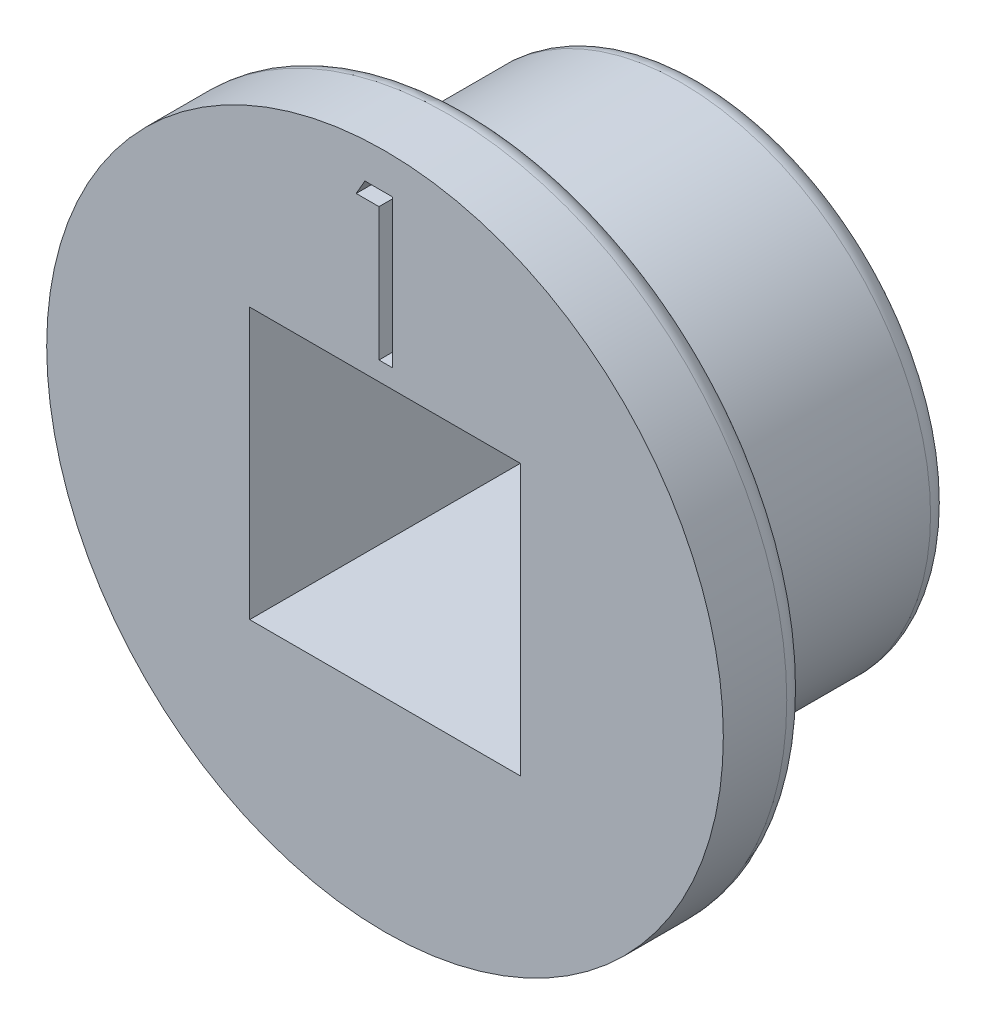
SolidWorks part; units mm, degrees
material "ABS"
ref_plane "Front Plane" through (0, 0, 0) normal (0, 0, 1) x (1, 0, 0)
ref_plane "Top Plane" through (0, 0, 0) normal (0, 1, 0) x (1, 0, 0)
ref_plane "Right Plane" through (0, 0, 0) normal (1, 0, 0) x (0, 0, -1)
sketch "Sketch1" plane through (0, 0, 0) normal (0, 0, 1) x (1, 0, 0)
  line L1 (-3.2, 3.2) -> (3.2, 3.2)
  line L2 (-3.2, 3.2) -> (-3.2, -3.2)
  line L3 (-3.2, -3.2) -> (3.2, -3.2)
  line L4 (3.2, 3.2) -> (3.2, -3.2)
  circle A0 centre (0, 0) radius 5.9
  circle A1 centre (0, 0) radius 8
  point P4 (0, 3.2)
  point P6 (-3.2, 0)
  dimension "D2" = 11.8
  dimension "D3" = 16
  dimension "D1" = 6.4
extrude "Boss-Extrude1" add sketch "Sketch1" against normal blind 5.5 contours A0 L1 L4 L3 L2 region at (-5.7331, 0, 0)
extrude "Boss-Extrude2" add sketch "Sketch1<3>" along normal blind 2 contours A1 A0 | A0 L1 L4 L3 L2 region at (-5.7331, 0, 0) region at (-7.7737, 0, 0)
sketch "Sketch1<3>" plane through (0, 0, 0) normal (0, 0, 1) x (1, 0, 0) same geometry as "Sketch1"
fillet "Fillet1" radius 0.5 2 edges at (8, 0, 0) (5.9, 0, -5.5)
sketch "Sketch2" plane through (0, 0, 2) normal (0, 0, 1) x (1, 0, 0)
  text T0 "1"
extrude "Cut-Extrude1" cut sketch "Sketch2" against normal blind 0.5
